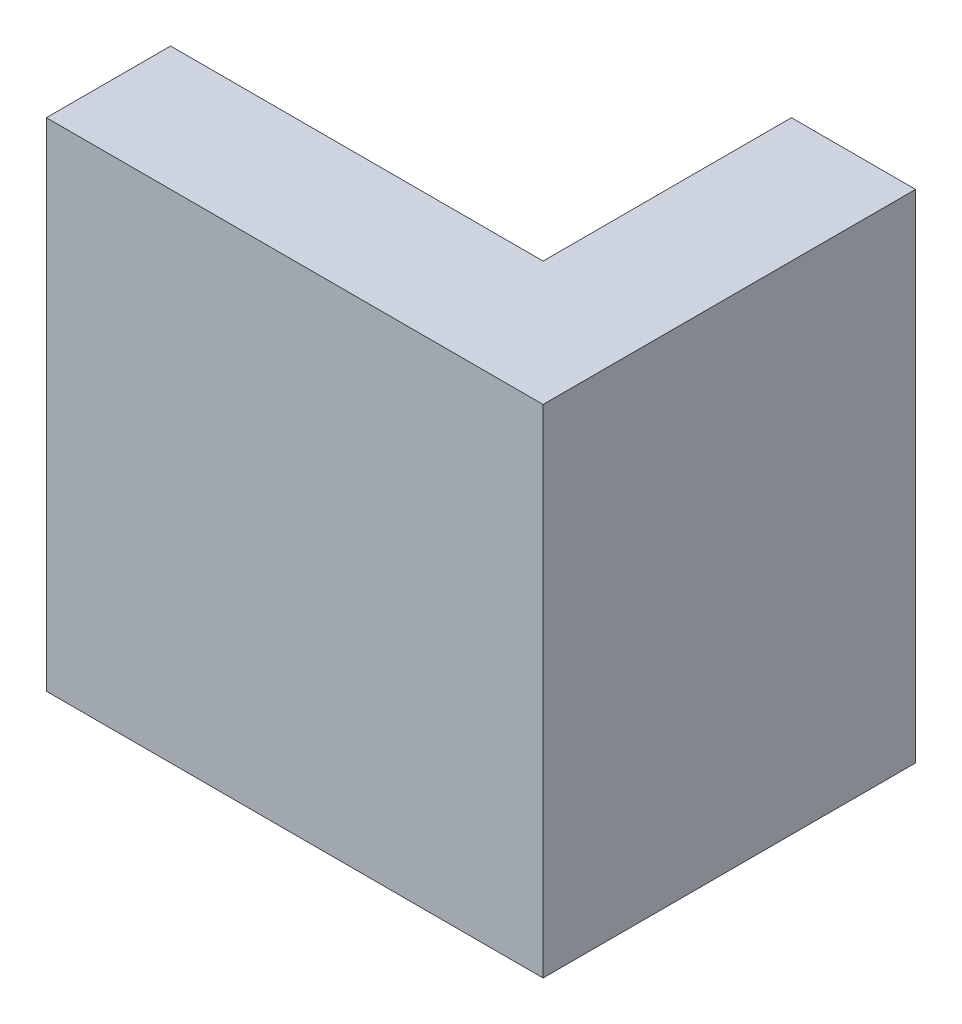
SolidWorks part; units mm, degrees
material "Acrylic (Medium-high impact)"
ref_plane "Front Plane" through (0, 0, 0) normal (0, 0, 1) x (1, 0, 0)
ref_plane "Top Plane" through (0, 0, 0) normal (0, 1, 0) x (1, 0, 0)
ref_plane "Right Plane" through (0, 0, 0) normal (1, 0, 0) x (0, 0, -1)
sketch "Sketch1" plane through (0, 0, 0) normal (0, 1, 0) x (1, 0, 0)
  line L1 (0, 0) -> (12.7, 0)
  line L2 (0, 0) -> (0, 3.175)
  line L3 (0, 3.175) -> (12.7, 3.175)
  line L4 (12.7, 0) -> (12.7, 3.175)
  dimension "D1" = 12.7
  dimension "D2" = 3.175
extrude "Boss-Extrude1" add sketch "Sketch1" along normal blind 12.7
sketch "Sketch2" plane through (0, 0, -3.175) normal (0, 0, -1) x (-1, 0, 0)
  line L5 (-12.7, 0) -> (0, 0) construction
  line L6 (-12.7, 12.7) -> (-9.525, 12.7)
  line L7 (-12.7, 12.7) -> (-12.7, 0)
  line L8 (-12.7, 0) -> (-9.525, 0)
  line L9 (-9.525, 12.7) -> (-9.525, 0)
  dimension "D1" = 3.175
extrude "Boss-Extrude2" add sketch "Sketch2" along normal blind 6.35
ref_plane "Plane1" through (0, 0, -3.175) normal (0, 0, -1) x (-1, 0, 0)
